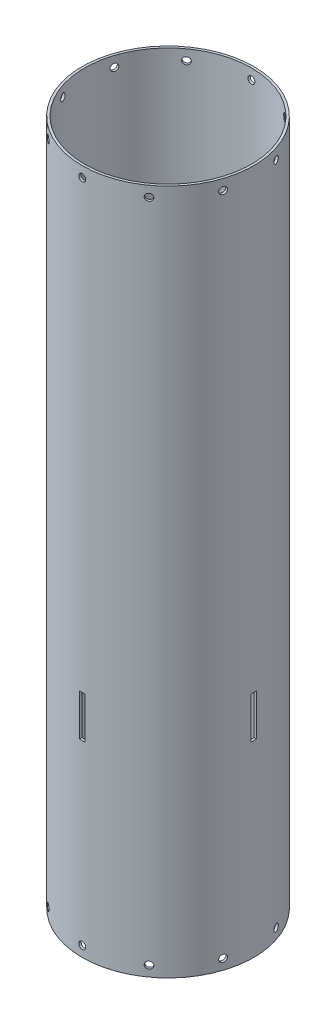
SolidWorks part; units mm, degrees
material "Fiberglass"
ref_plane "Front Plane" through (0, 0, 0) normal (0, 0, 1) x (1, 0, 0)
ref_plane "Top Plane" through (0, 0, 0) normal (0, 1, 0) x (1, 0, 0)
ref_plane "Right Plane" through (0, 0, 0) normal (1, 0, 0) x (0, 0, -1)
sketch "Sketch1" plane through (0, 0, 0) normal (0, 1, 0) x (1, 0, 0)
  circle A0 centre (0, 0) radius 76.2
  circle A1 centre (0, 0) radius 78.359
  dimension "D1" = 152.4
  dimension "D2" = 156.718
extrude "Boss-Extrude1" add sketch "Sketch1" along normal blind 626.11
sketch "Sketch2" plane through (0, 0, 0) normal (0, 0, 1) x (1, 0, 0)
  line L0 (0, 0) -> (0, 105.6712) construction
  line L1 (-76.2, 0) -> (76.2, 0) construction
  line L2 (-78.359, 0) -> (78.359, 0) construction
  line L3 (78.359, 313.055) -> (42.8908, 313.055) construction
  line L4 (78.359, 0) -> (78.359, 626.11) construction
  circle A0 centre (0, 9.525) radius 3.175
  circle A1 centre (0, 616.585) radius 3.175
  dimension "D1" = 6.35
  dimension "D2" = 9.525
extrude "Cut-Extrude1" cut sketch "Sketch2" against normal through all
ref_axis "Axis1" through (0, 0, 0) along (0, 1, 0)
pattern_circular "CirPattern1" count 10 over 360 about axis through (0, 0, 0) along (0, 1, 0) of "Cut-Extrude1" reverse direction yes
sketch "Sketch3" plane through (0, 0, 0) normal (0, 0, 1) x (1, 0, 0)
  line L0 (0, 0) -> (0, 105.6712) construction
  line L1 (-2.54, 171.45) -> (2.54, 171.45)
  line L2 (-2.54, 171.45) -> (-2.54, 209.55)
  line L3 (-2.54, 209.55) -> (2.54, 209.55)
  line L4 (2.54, 171.45) -> (2.54, 209.55)
  line L5 (-2.54, 171.45) -> (2.54, 209.55) construction
  line L6 (-2.54, 209.55) -> (2.54, 171.45) construction
  line L7 (-76.2, 0) -> (76.2, 0) construction
  line L8 (0, 626.11) -> (0, 408.1695) construction
  line L9 (76.2, 626.11) -> (-76.2, 626.11) construction
  point P0 (0, 190.5)
  dimension "D1" = 171.45
  dimension "D2" = 38.1
  dimension "D3" = 5.08
extrude "Cut-Extrude2" cut sketch "Sketch3" against normal through all
ref_axis "Axis2" through (0, 626.11, 0) along (0, -1, 0)
pattern_circular "CirPattern2" count 4 over 360 about axis through (0, 626.11, 0) along (0, -1, 0) of "Cut-Extrude2"
